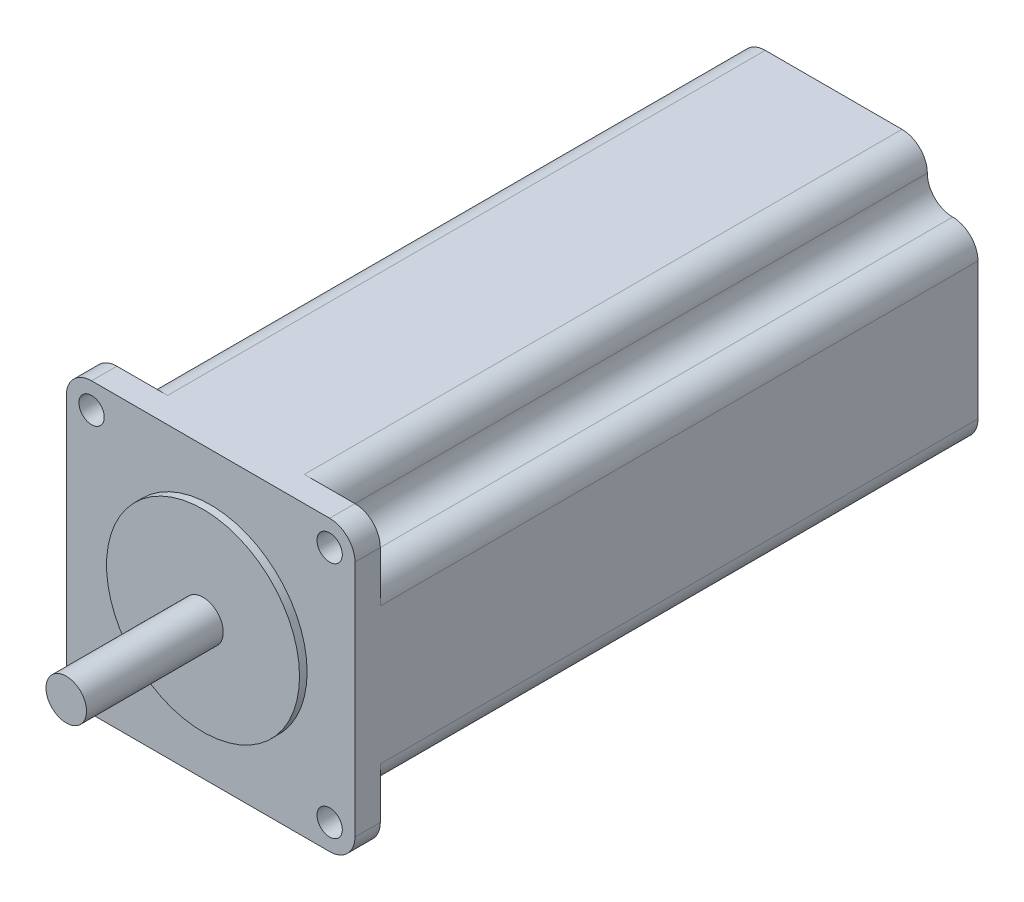
SolidWorks part; units mm, degrees
ref_plane "Front Plane" through (0, 0, 0) normal (0, 0, 1) x (1, 0, 0)
ref_plane "Top Plane" through (0, 0, 0) normal (0, 1, 0) x (1, 0, 0)
ref_plane "Right Plane" through (0, 0, 0) normal (1, 0, 0) x (0, 0, -1)
sketch "Sketch1" plane through (0, 0, 0) normal (0, 0, 1) x (1, 0, 0)
  line L1 (-33.3612, 31.2642) -> (23.6388, 31.2642)
  line L2 (-33.3612, 31.2642) -> (-33.3612, -25.7358)
  line L3 (-33.3612, -25.7358) -> (23.6388, -25.7358)
  line L4 (23.6388, 31.2642) -> (23.6388, -25.7358)
  dimension "D1" = 57
  dimension "D2" = 57
extrude "Boss-Extrude1" add sketch "Sketch1" along normal blind 123
sketch "Sketch2" plane through (0, 0, 0) normal (0, 0, -1) x (-1, 0, 0)
  line L1 (-23.6388, 31.2642) -> (-13.6388, 31.2642)
  line L2 (-23.6388, 31.2642) -> (-23.6388, 21.2642)
  line L3 (-23.6388, 21.2642) -> (-13.6388, 21.2642)
  line L4 (-13.6388, 31.2642) -> (-13.6388, 21.2642)
  dimension "D1" = 10
  dimension "D2" = 10
extrude "Cut-Extrude1" cut sketch "Sketch2" against normal blind 118
pattern_linear "LPattern1" count 2 spacing 47 along (-1, 0, 0) count 2 spacing 47 along (0, -1, 0) of "Cut-Extrude1"
sketch "Sketch3" plane through (0, 0, 123) normal (0, 0, 1) x (1, 0, 0)
  line L0 (23.6388, 31.2642) -> (-33.3612, 31.2642) construction
  line L1 (-33.3612, 31.2642) -> (-33.3612, -25.7358) construction
  circle A0 centre (-28.3612, 26.2642) radius 2.5
  dimension "D3" = 5
  dimension "D1" = 5
  dimension "D2" = 5
extrude "Cut-Extrude2" cut sketch "Sketch3" against normal blind 50
pattern_linear "LPattern2" count 2 spacing 47 along (1, 0, 0) count 2 spacing 47 along (0, -1, 0) of "Cut-Extrude2"
fillet "Fillet1" radius 5 16 edges at (-33.3612, 21.2642, 59) (-23.3612, 21.2642, 59) (-23.3612, 31.2642, 59) (13.6388, 31.2642, 59) (13.6388, 21.2642, 59) (23.6388, 21.2642, 59) (23.6388, -25.7358, 120.5) (23.6388, -15.7358, 59) (13.6388, -15.7358, 59) (13.6388, -25.7358, 59) (-23.3612, -25.7358, 59) (-23.3612, -15.7358, 59) (-33.3612, -15.7358, 59) (-33.3612, -25.7358, 120.5) (-33.3612, 31.2642, 120.5) (23.6388, 31.2642, 120.5)
sketch "Sketch5" plane through (0, 0, 123) normal (0, 0, 1) x (1, 0, 0)
  line L0 (18.6388, 31.2642) -> (-28.3612, 31.2642) construction
  line L1 (-33.3612, 26.2642) -> (-33.3612, -20.7358) construction
  circle A0 centre (-4.8612, 2.7642) radius 19.05
  dimension "D1" = 28.5
  dimension "D2" = 28.5
extrude "Boss-Extrude3" add sketch "Sketch5" along normal blind 1.5
sketch "Sketch4" plane through (0, 0, 123) normal (0, 0, 1) x (1, 0, 0)
  line L0 (18.6388, 31.2642) -> (-28.3612, 31.2642) construction
  line L1 (23.6388, -20.7358) -> (23.6388, 26.2642) construction
  circle A0 centre (-4.8612, 2.7642) radius 4
  dimension "D3" = 8
  dimension "D1" = 28.5
  dimension "D2" = 28.5
extrude "Boss-Extrude2" add sketch "Sketch4" along normal blind 28.5
